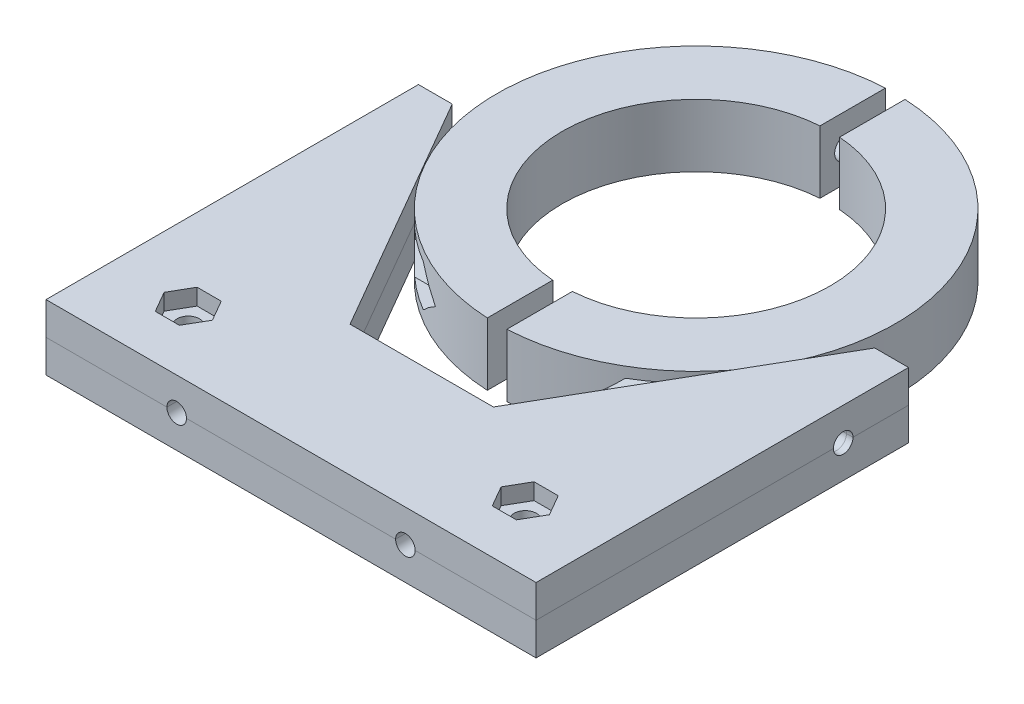
SolidWorks part; units mm, degrees
ref_plane "前基準面" through (0, 0, 0) normal (0, 0, 1) x (1, 0, 0)
ref_plane "上基準面" through (0, 0, 0) normal (0, 1, 0) x (1, 0, 0)
ref_plane "右基準面" through (0, 0, 0) normal (1, 0, 0) x (0, 0, -1)
sketch "草圖2" plane through (0, 0, 0) normal (0, 1, 0) x (1, 0, 0)
  circle A0 centre (0, 0) radius 20.5
  dimension "D1" = 41
sketch "草圖3" plane through (0, 0, 0) normal (1, 0, 0) x (0, 0, -1)
  line L0 (20.5, 0) -> (-20.5, 0) construction
  line L1 (20.5, 0) -> (-20.5, 0) construction
  line L3 (20.5, 4.8) -> (30.5, 4.8)
  line L4 (20.5, 4.8) -> (20.5, -4.8)
  line L5 (20.5, -4.8) -> (30.5, -4.8)
  line L6 (30.5, 4.8) -> (30.5, -4.8)
  point P8 (20.5, 0)
  dimension "D1" = 10
  dimension "D2" = 9.6
sweep "掃出1" add profiles "草圖3" path "草圖2"
sketch "草圖5" plane through (0, 0, 0) normal (0, 1, 0) x (1, 0, 0)
  line L0 (-30.5, 0) -> (30.5, 0) construction
  line L1 (-30.5, 50) -> (1.5, 50)
  line L2 (-30.5, 50) -> (-30.5, -50)
  line L3 (-30.5, -50) -> (1.5, -50)
  line L4 (1.5, 50) -> (1.5, -50)
  circle A0 centre (0, 0) radius 30.5 construction
  point P4 (-36.9864, -50)
  point P5 (2.7656, 50)
  point P6 (-30.5, 0)
  dimension "D1" = 1.5
  dimension "D2" = 100
extrude "除料-伸長1" cut sketch "草圖5" against normal through all both and the other way through all contours L1 L4 L3 L2
ref_plane "平面1" through (30.5, 0, 0) normal (1, 0, 0) x (0, 0, -1)
sketch "草圖6" plane through (30.5, 0, 0) normal (1, 0, 0) x (0, 0, -1)
  line L0 (0, 0) -> (0, -9.0499) construction
  line L2 (28.1401, 0) -> (26.2926, 3.2)
  line L3 (26.2926, 3.2) -> (22.5975, 3.2)
  line L4 (20.445, 4.8) -> (20.445, -4.8)
  line L5 (30.4631, 4.8) -> (20.445, 4.8)
  line L6 (30.4631, -4.8) -> (30.4631, 4.8)
  line L7 (20.445, -4.8) -> (30.4631, -4.8)
  line L8 (20.445, 4.8) -> (20.445, -4.8) construction
  line L9 (30.4631, 4.8) -> (20.445, 4.8) construction
  line L10 (30.4631, -4.8) -> (30.4631, 4.8) construction
  line L11 (20.445, -4.8) -> (30.4631, -4.8) construction
  line L12 (22.5975, 3.2) -> (20.75, 0)
  line L13 (20.75, 0) -> (22.5975, -3.2)
  line L14 (22.5975, -3.2) -> (26.2926, -3.2)
  line L15 (26.2926, -3.2) -> (28.1401, 0)
  line L16 (-20.75, 0) -> (-22.5975, 3.2)
  line L17 (-22.5975, 3.2) -> (-26.2926, 3.2)
  line L18 (-26.2926, 3.2) -> (-28.1401, 0)
  line L19 (-28.1401, 0) -> (-26.2926, -3.2)
  line L20 (-26.2926, -3.2) -> (-22.5975, -3.2)
  line L21 (-22.5975, -3.2) -> (-20.75, 0)
  circle A0 centre (24.445, 0) radius 4.8 construction
  circle A1 centre (-24.445, 0) radius 4.8 construction
  circle A2 centre (24.445, 0) radius 3.2 construction
  circle A3 centre (-24.445, 0) radius 3.2 construction
  point P7 (0, 0)
  point P9 (20.445, 0)
  dimension "D2" = 4
  dimension "D3" = 6.4
  dimension "D1" = 0
hole_wizard "Ø3.5 (3.5) 直徑孔1" positions "草圖7" profile "草圖9" hole size "Ø3.5" standard "ISO" end condition through all
sketch "草圖7" plane through (30.5, 0, 0) normal (1, 0, 0) x (0, 0, -1)
  point P0 (-24.445, 0)
  point P3 (24.445, 0)
sketch "草圖9" plane through (30.5, 0, 24.445) normal (0, 1, 0) x (0, 0, -1)
  line L0 (0, 0) -> (0, 29)
  line L1 (0, 29) -> (1.75, 29)
  line L2 (1.75, 29) -> (1.75, 0)
  line L5 (1.75, 0) -> (0, 0)
  line L11 (0, -6.35) -> (0, 107.95) construction
  dimension "貫穿孔直徑" = 3.5
  dimension "貫穿孔深度" = 29
extrude "除料-伸長5" cut sketch "草圖6" against normal blind 23 contours L2 L3 L12 L13 L14 L15 | L17 L18 L19 L20 L21 L16
mirror "鏡射8" about plane through (0, 0, 0) normal (1, 0, 0) of bodies 118
sketch "草圖12" plane through (0, 0, 0) normal (0, 1, 0) x (1, 0, 0)
  line L0 (-32.3316, -5) -> (-10.9697, -42)
  line L5 (10.9697, -42) -> (32.3316, -5)
  line L6 (32.3316, -5) -> (37.5, -5)
  line L7 (-37.5, -5) -> (-32.3316, -5)
  line L8 (-37.5, -5) -> (-37.5, -62)
  line L9 (-37.5, -62) -> (37.5, -62)
  line L10 (37.5, -5) -> (37.5, -62)
  line L11 (-10.9697, -42) -> (10.9697, -42)
  line L13 (-1.5, 5) -> (1.5, 5) construction
  line L14 (-1.5, 5) -> (-1.5, -28) construction
  line L15 (-1.5, -28) -> (1.5, -28) construction
  line L16 (1.5, 5) -> (1.5, -28) construction
  arc A0 (1.5, -30.4631) -> (1.5, 30.4631) centre (0, 0) ccw construction
  arc A1 (1.5, -30.4631) -> (1.5, 30.4631) centre (0, 0) ccw construction
  arc A2 (1.5, -30.4631) -> (1.5, 30.4631) centre (0, 0) ccw construction
  arc A3 (1.5, -30.4631) -> (1.5, 30.4631) centre (0, 0) ccw construction
  arc A4 (1.5, 30.4631) -> (1.5, -30.4631) centre (0, 0) ccw construction
  point P1 (-30.5, 0)
  point P2 (0, 5)
  point P6 (0, -42)
  point P16 (0, -62)
  dimension "D8" = 5
  dimension "D9" = 34
  dimension "D1" = 5
  dimension "D2" = 62
  dimension "D3" = 75
  dimension "D4" = 20
  dimension "D5" = 120
  dimension "D6" = 3
  dimension "D7" = 33
extrude "填料-伸長1" add sketch "草圖12" against normal blind 5 separate body contours L8 L9 L10 L6 L5 L11 L0 L7
sketch "草圖14" plane through (0, 0, 42) normal (0, 0, 1) x (1, 0, 0)
  line L4 (-10.9697, 0) -> (10.9697, 0) construction
  circle A2 centre (0, 0) radius 1.5
  point P2 (0, 0)
  dimension "D1" = 3
sketch "草圖17" plane through (0, -5, 0) normal (0, -1, 0) x (-1, 0, 0)
  line L0 (37.5, -15) -> (36.5, -15)
  line L2 (37.5, -5) -> (37.5, -62) construction
  line L3 (33.5, -18) -> (33.5, -55.5)
  line L4 (30.5, -58.5) -> (0, -58.5)
  line L8 (0, -58.5) -> (0, -42)
  line L9 (10.9697, -42) -> (-10.9697, -42) construction
  line L10 (37.5, -62) -> (-37.5, -62) construction
  line L11 (37.5, -5) -> (32.3316, -5) construction
  arc A0 (30.5, -58.5) -> (33.5, -55.5) centre (30.5, -55.5) ccw
  arc A1 (33.5, -18) -> (36.5, -15) centre (36.5, -18) cw
  dimension "D1" = 3
  dimension "D2" = 4
  dimension "D3" = 3.5
  dimension "D4" = 10
sweep "除料-掃出2" cut profiles "草圖14" path "草圖17"
sketch "草圖18" plane through (0, -5, 0) normal (0, -1, 0) x (-1, 0, 0)
  line L0 (0, -42) -> (0, -58.5)
  line L1 (37.5, -62) -> (-37.5, -62) construction
  line L2 (0, -58.5) -> (17.5, -58.5)
  line L3 (17.5, -58.5) -> (17.5, -62)
  line L5 (10.9697, -42) -> (-10.9697, -42) construction
  line L6 (-1.5, -60) -> (1.5, -57) construction
  line L7 (-1.5, -60) -> (1.5, -57) construction
  line L8 (37.5, -16.5) -> (37.5, -62) construction
  point P8 (25.5255, -58.5)
  point P10 (0, 0)
  point P13 (0, -52.1363)
  point P16 (0, -58.5)
  dimension "D1" = 20
sweep "除料-掃出3" cut profiles "草圖14<3>" path "草圖18"
sketch "草圖14<3>" plane through (0, 0, 42) normal (0, 0, 1) x (1, 0, 0) same geometry as "草圖14"
mirror "鏡射2" about plane through (0, 0, 0) normal (1, 0, 0) of "除料-掃出3", "除料-掃出2"
sketch "草圖19" plane through (0, -5, 0) normal (0, 1, 0) x (-1, 0, 0)
  line L0 (-25.8418, 52) -> (25.7287, 52) construction
  line L3 (37.5, 62) -> (-37.5, 62) construction
  line L5 (22.0337, 52) -> (23.8812, 48.8)
  line L6 (23.8812, 48.8) -> (27.5762, 48.8)
  line L7 (27.5762, 48.8) -> (29.4237, 52)
  line L8 (29.4237, 52) -> (27.5762, 55.2)
  line L9 (27.5762, 55.2) -> (23.8812, 55.2)
  line L10 (23.8812, 55.2) -> (22.0337, 52)
  line L11 (-29.5369, 52) -> (-27.6893, 48.8)
  line L12 (-27.6893, 48.8) -> (-23.9943, 48.8)
  line L13 (-23.9943, 48.8) -> (-22.1468, 52)
  line L14 (-22.1468, 52) -> (-23.9943, 55.2)
  line L15 (-23.9943, 55.2) -> (-27.6893, 55.2)
  line L16 (-27.6893, 55.2) -> (-29.5369, 52)
  circle A0 centre (25.7287, 52) radius 3.2 construction
  circle A1 centre (-25.8418, 52) radius 3.2 construction
  point P2 (-25.8418, 52)
  point P3 (25.7287, 52)
  dimension "D4" = 6.4
  dimension "D3" = 10
hole_wizard "Ø3.4 (3.4) 直徑孔1" positions "草圖20" profile "草圖21" hole size "Ø3.4" standard "ISO"
sketch "草圖20" plane through (0, 0, 0) normal (0, 1, 0) x (1, 0, 0)
  point P0 (25.8418, -52)
  point P3 (-25.7287, -52)
sketch "草圖21" plane through (25.8418, 0, 52) normal (1, 0, 0) x (0, 0, 1)
  line L0 (0, 0) -> (0, 11.0215)
  line L1 (0, 11.0215) -> (1.7, 10)
  line L2 (1.7, 10) -> (1.7, 0)
  line L5 (1.7, 0) -> (0, 0)
  line L10 (0, 11.0215) -> (-1.7, 10) construction
  line L11 (0, -6.35) -> (0, 107.95) construction
  dimension "鑽孔直徑" = 3.4
  dimension "鑽孔深度" = 10
  dimension "導頭角度" = 118
extrude "除料-伸長4" cut sketch "草圖19" along normal blind 2.5 contours L16 L15 L14 L13 L12 L11 | L10 L9 L8 L7 L6 L5 region at (-25.7287, -5, 52) region at (25.8418, -5, 52)
mirror "鏡射9" about plane through (0, 0, 0) normal (0, 1, 0) of bodies 117
